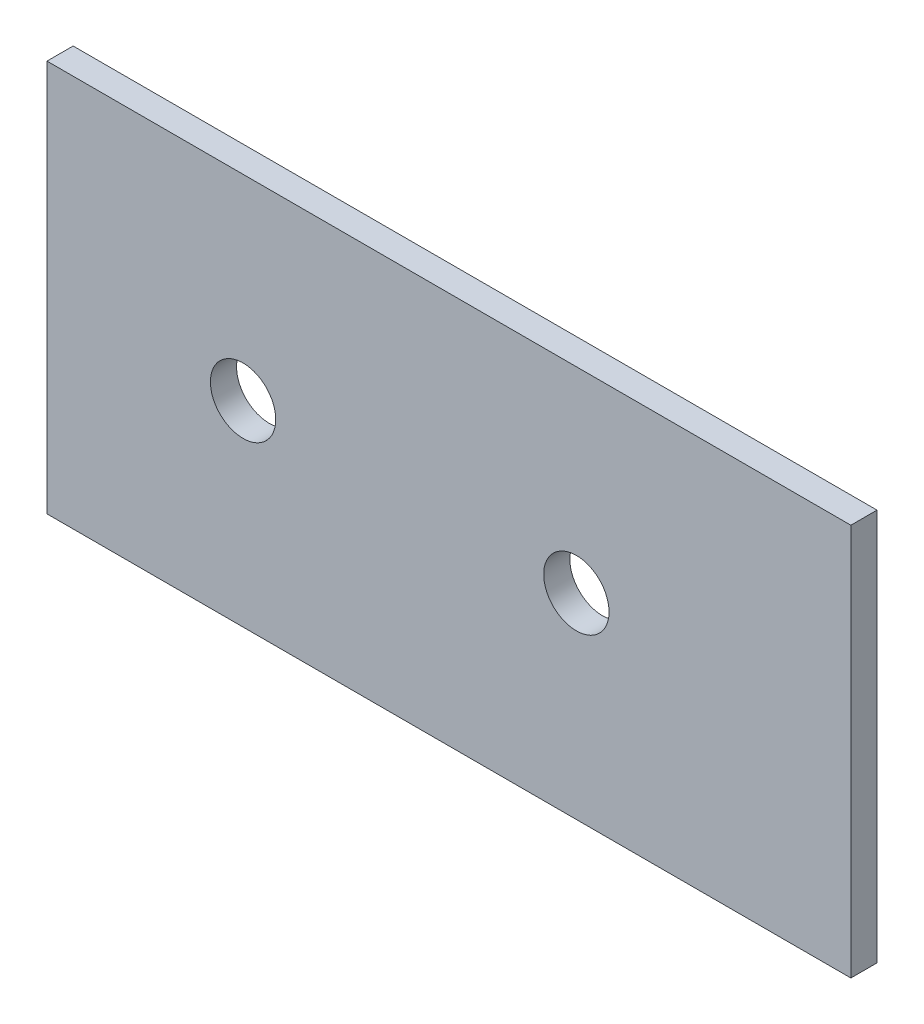
SolidWorks part; units mm, degrees
ref_plane "Front Plane" through (0, 0, 0) normal (0, 0, 1) x (1, 0, 0)
ref_plane "Top Plane" through (0, 0, 0) normal (0, 1, 0) x (1, 0, 0)
ref_plane "Right Plane" through (0, 0, 0) normal (1, 0, 0) x (0, 0, -1)
sketch "Sketch1" plane through (0, 0, 0) normal (0, 0, 1) x (1, 0, 0)
  line L1 (-81, -30) -> (42, -30)
  line L2 (-81, -30) -> (-81, 30)
  line L3 (-81, 30) -> (42, 30)
  line L4 (42, -30) -> (42, 30)
  circle A0 centre (0, 0) radius 5
  circle A2 centre (-51, 0) radius 5
  point P1 (0, 0)
  point P8 (-81, 0)
  dimension "D3" = 10
  dimension "D4" = 0
  dimension "D1" = 30
  dimension "D2" = 60
  dimension "D8" = 51
  dimension "D9" = 42
extrude "Boss-Extrude1" add sketch "Sketch1" along normal blind 4
